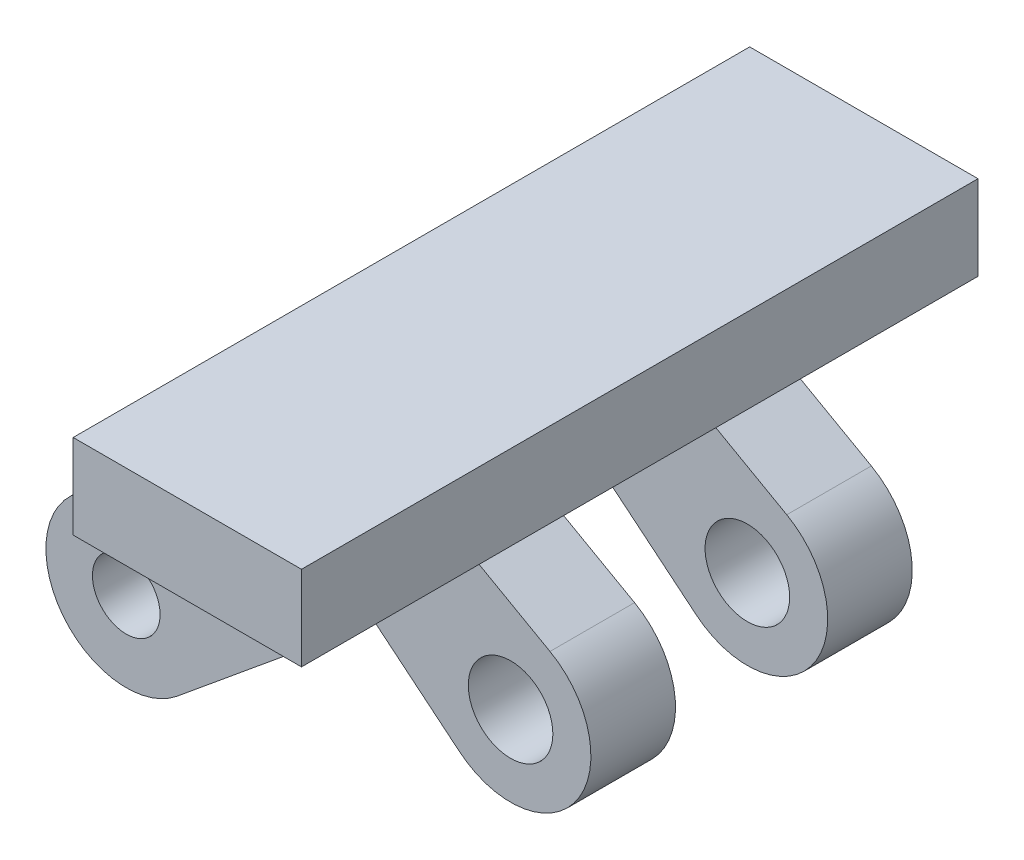
SolidWorks part; units mm, degrees
ref_plane "前视基准面" through (0, 0, 0) normal (0, 0, 1) x (1, 0, 0)
ref_plane "上视基准面" through (0, 0, 0) normal (0, 1, 0) x (1, 0, 0)
ref_plane "右视基准面" through (0, 0, 0) normal (1, 0, 0) x (0, 0, -1)
sketch "草图1" plane through (0, 0, 0) normal (0, 0, 1) x (1, 0, 0)
  line L1 (0, 0) -> (5.4, 0)
  line L2 (0, 0) -> (0, -2)
  line L3 (0, -2) -> (5.4, -2)
  line L4 (5.4, 0) -> (5.4, -2)
  dimension "D1" = 2
  dimension "D2" = 5.4
extrude "凸台-拉伸1" add sketch "草图1" along normal blind 8 and the other way blind 8
ref_plane "基准面2" through (0, 0, 6) normal (0, 0, 1) x (1, 0, 0)
sketch "草图3" plane through (0, 0, 6) normal (0, 0, 1) x (1, 0, 0)
  line L0 (0, -2) -> (-1.6772, -2.9444)
  line L1 (5.4, -2) -> (0.463, -6.0666)
  line L2 (0, -2) -> (5.4, -2) construction
  line L3 (0, -2) -> (5.4, -2)
  circle A0 centre (-0.745, -4.6) radius 1.9
  circle A1 centre (-0.745, -4.6) radius 0.8
  point P14 (2.7, -2)
  dimension "D1" = 1.6
  dimension "D2" = 3.8
  dimension "D3" = 2.6
  dimension "D4" = 3.445
extrude "凸台-拉伸2" add sketch "草图3" against normal blind 2 contours A0 A1 | A0 L1 L3 L0 region at (2.0907, -3.0871, 6) region at (0.1867, -3.0061, 6)
ref_plane "基准面1" through (0, 0, 3.8) normal (0, 0, 1) x (1, 0, 0)
sketch "草图5" plane through (0, 0, 3.8) normal (0, 0, 1) x (1, 0, 0)
  line L0 (5.4, -2) -> (7.0772, -2.9444)
  line L1 (0, -2) -> (4.937, -6.0666)
  line L2 (6.145, -4.6) -> (-0.745, -4.6) construction
  line L3 (0, -2) -> (5.4, -2)
  line L4 (0, -2) -> (5.4, -2) construction
  circle A0 centre (6.145, -4.6) radius 1.9
  circle A1 centre (6.145, -4.6) radius 1
  point P7 (0.6627, -2)
  point P9 (4.8494, -2)
  dimension "D1" = 3.8
  dimension "D2" = 2
  dimension "D3" = 6.89
extrude "凸台-拉伸3" add sketch "草图5" against normal blind 2 contours L2 A0 L0 L3 L1 | A1 A0 | A0 L2 L1 region at (3.2647, -2.9594, 3.8) region at (7.7389, -3.6683, 3.8) region at (3.9765, -4.9977, 3.8)
mirror "镜向1" about plane through (0, 0, 0) normal (0, 0, 1) of "凸台-拉伸2", "凸台-拉伸3"
